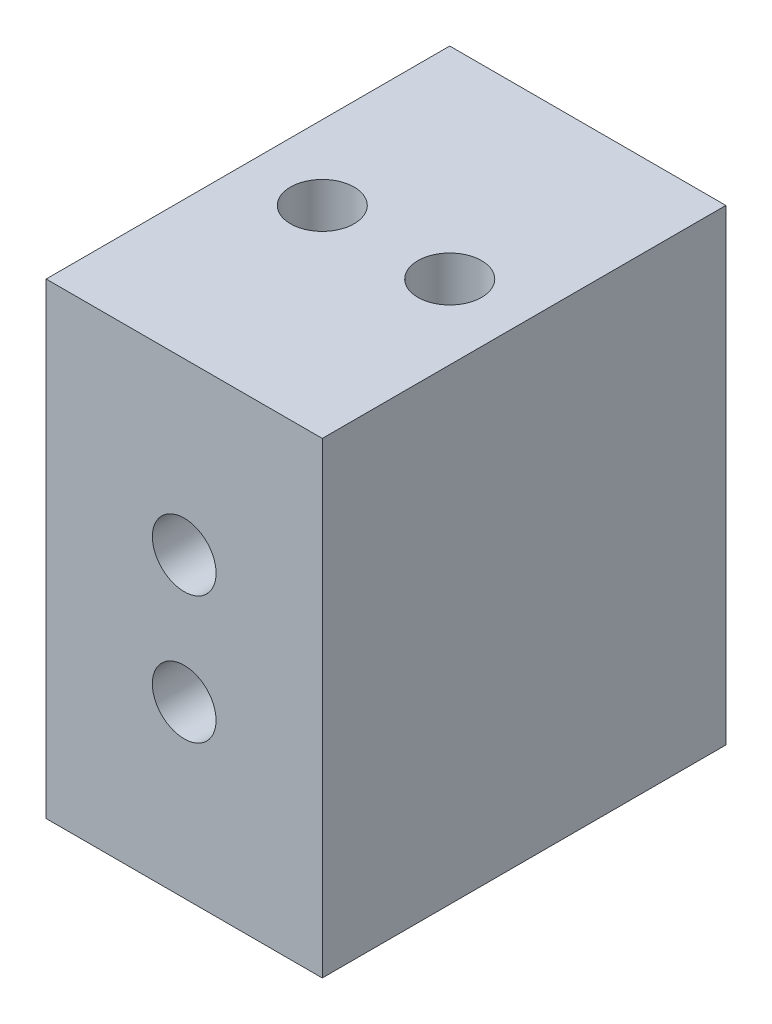
SolidWorks part; units mm, degrees
ref_plane "Front Plane" through (0, 0, 0) normal (0, 0, 1) x (1, 0, 0)
ref_plane "Top Plane" through (0, 0, 0) normal (0, 1, 0) x (1, 0, 0)
ref_plane "Right Plane" through (0, 0, 0) normal (1, 0, 0) x (0, 0, -1)
sketch "Sketch1" plane through (0, 0, 0) normal (0, 1, 0) x (1, 0, 0)
  line L1 (-6.5, 9.5) -> (6.5, 9.5)
  line L2 (-6.5, 9.5) -> (-6.5, -9.5)
  line L3 (-6.5, -9.5) -> (6.5, -9.5)
  line L4 (6.5, 9.5) -> (6.5, -9.5)
  line L5 (-6.5, 9.5) -> (6.5, -9.5) construction
  line L6 (-6.5, -9.5) -> (6.5, 9.5) construction
  point P0 (0, 0)
  dimension "D1" = 19
  dimension "D2" = 13
extrude "Boss-Extrude1" add sketch "Sketch1" along normal blind 22
sketch "Sketch3" plane through (0, 0, 9.5) normal (0, 0, 1) x (1, 0, 0)
  line L0 (6.5, 11) -> (0, 11) construction
  line L1 (6.5, 22) -> (6.5, 0) construction
  line L2 (0, 11) -> (0, 14) construction
  circle A0 centre (0, 14) radius 1.5
  circle A1 centre (0, 8) radius 1.5
  dimension "D2" = 3
  dimension "D1" = 3
extrude "Cut-Extrude1" cut sketch "Sketch3" against normal blind 8
sketch "Sketch4" plane through (0, 22, 0) normal (0, 1, 0) x (1, 0, 0)
  line L0 (0, 0) -> (3, 0) construction
  line L1 (0, -10.45) -> (0, 10.45) construction
  circle A0 centre (3, 0) radius 1.5
  circle A1 centre (-3, 0) radius 1.5
  dimension "D2" = 3
  dimension "D1" = 3
extrude "Cut-Extrude2" cut sketch "Sketch4" against normal up to surface (22 mm away) up to face at (0, 0, 0)
